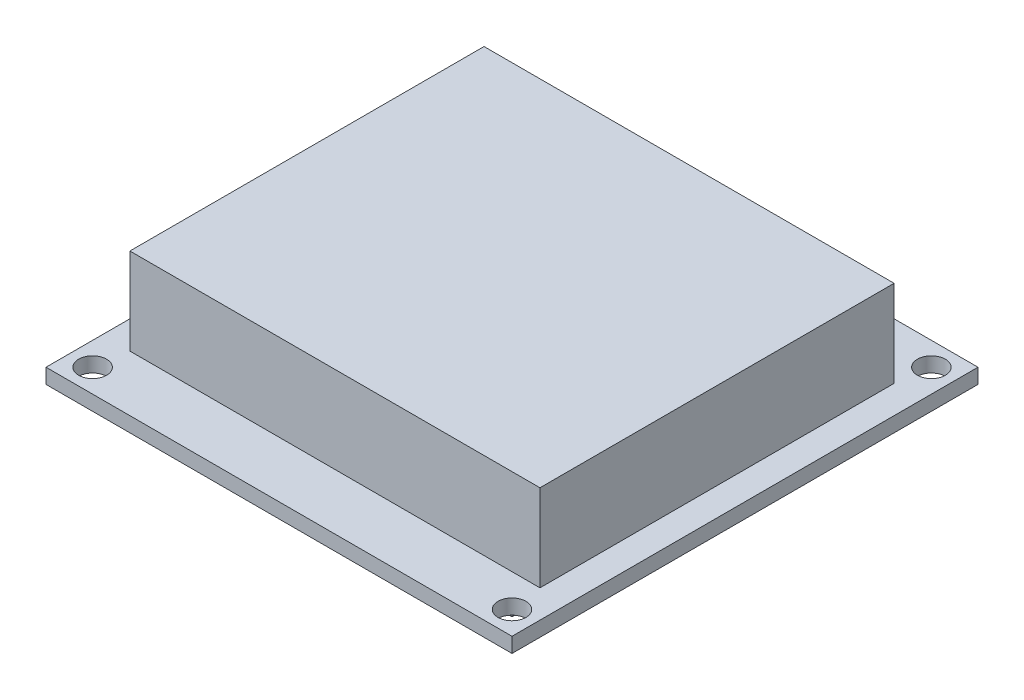
SolidWorks part; units mm, degrees
ref_plane "Front Plane" through (0, 0, 0) normal (0, 0, 1) x (1, 0, 0)
ref_plane "Top Plane" through (0, 0, 0) normal (0, 1, 0) x (1, 0, 0)
ref_plane "Right Plane" through (0, 0, 0) normal (1, 0, 0) x (0, 0, -1)
sketch "SK_Board" plane through (0, 0, 0) normal (0, 1, 0) x (1, 0, 0)
  line L1 (-25, 25) -> (25, 25)
  line L2 (-25, 25) -> (-25, -25)
  line L3 (-25, -25) -> (25, -25)
  line L4 (25, 25) -> (25, -25)
  dimension "D1" = 50
  dimension "D2" = 50
  dimension "D3" = 25
  dimension "D4" = 25
extrude "EX_Board" add sketch "SK_Board" along normal blind 1.6
sketch "SK_MountHoles_4x" plane through (0, 0, 0) normal (0, 1, 0) x (1, 0, 0)
  circle A0 centre (22.5, -22.5) radius 1.5
  circle A1 centre (-22.5, -22.5) radius 1.5
  circle A2 centre (22.5, 22.5) radius 1.5
  circle A3 centre (-22.5, 22.5) radius 1.5
  dimension "D3" = 3
  dimension "D6" = 3
  dimension "D9" = 3
  dimension "D12" = 3
  dimension "D1" = 22.5
  dimension "D2" = 22.5
  dimension "D4" = 22.5
  dimension "D5" = 22.5
  dimension "D7" = 22.5
  dimension "D8" = 22.5
  dimension "D10" = 22.5
  dimension "D11" = 22.5
extrude "CUT_MountHoles_4x" cut sketch "SK_MountHoles_4x" along normal blind 1.6
ref_plane "PL_Zp1_6" through (0, 1.6, 0) normal (0, 1, 0) x (1, 0, 0)
sketch "SK_Components" plane through (0, 1.6, 0) normal (0, 1, 0) x (1, 0, 0)
  line L1 (-22, 19) -> (22, 19)
  line L2 (-22, 19) -> (-22, -19)
  line L3 (-22, -19) -> (22, -19)
  line L4 (22, 19) -> (22, -19)
  dimension "D1" = 38
  dimension "D2" = 44
  dimension "D3" = 19
  dimension "D4" = 22
extrude "EX_Components" add sketch "SK_Components" along normal blind 9.3
sketch "SK_Pins" plane through (0, 0, 0) normal (0, 1, 0) x (1, 0, 0)
  line L1 (-20, 20) -> (20, 20)
  line L2 (-20, 20) -> (-20, -20)
  line L3 (-20, -20) -> (20, -20)
  line L4 (20, 20) -> (20, -20)
  dimension "D1" = 40
  dimension "D2" = 40
  dimension "D3" = 20
  dimension "D4" = 20
extrude "EX_Pins" add sketch "SK_Pins" against normal blind 1.6
ref_axis "AX_X" through (0, 0, -27.5) along (0, 0, 1)
ref_axis "AX_Y" through (27.5, 0, 0) along (-1, 0, 0)
ref_axis "AX_Z" through (0, 11.525, 0) along (0, -1, 0)
